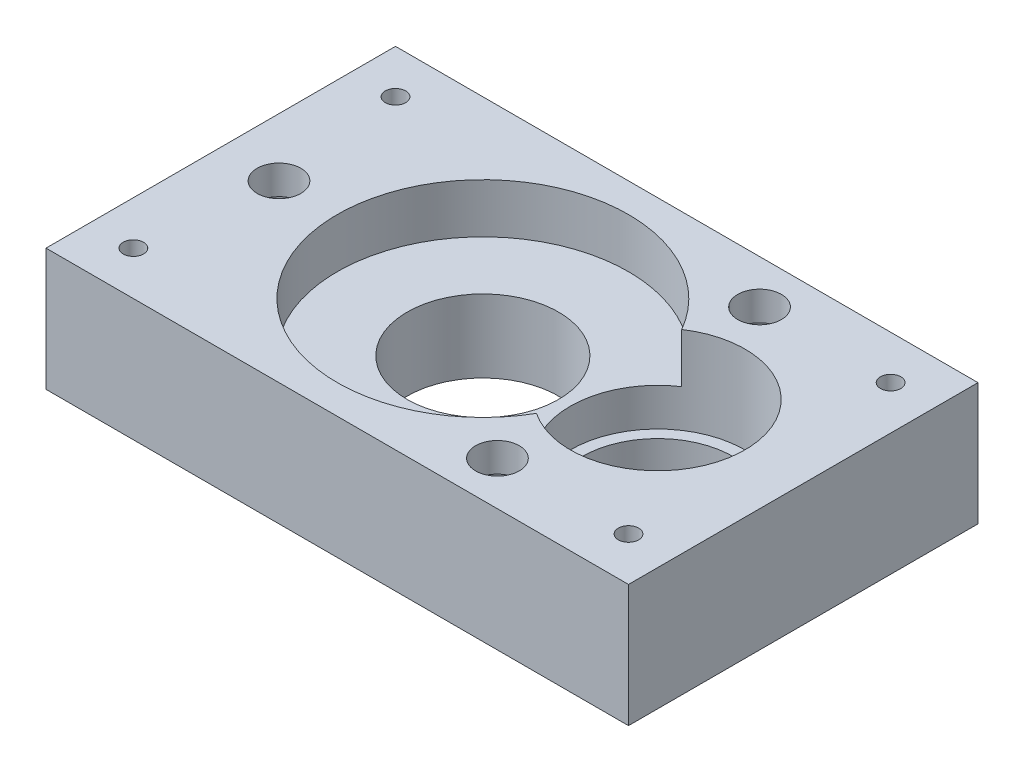
SolidWorks part; units mm, degrees
note: The reader was unsure of these and kept them because the rebuilt part matched: shared geometry of "草图1<13>", "草图1<14>", "草图3<4>".
ref_plane "前视基准面" through (0, 0, 0) normal (0, 0, 1) x (1, 0, 0)
ref_plane "上视基准面" through (0, 0, 0) normal (0, 1, 0) x (1, 0, 0)
ref_plane "右视基准面" through (0, 0, 0) normal (1, 0, 0) x (0, 0, -1)
other "Configuration Table"
sketch "草图1" plane through (0, 0, 0) normal (0, 1, 0) x (1, 0, 0)
  line L1 (0, 0) -> (20, 0)
  line L2 (0, 0) -> (0, -12)
  line L3 (0, -12) -> (20, -12)
  line L4 (20, 0) -> (20, -12)
  circle A4 centre (15, -6) radius 2.6
  circle A6 centre (7.8259, -8.9706) radius 0.6
  circle A8 centre (9.8163, -3.6294) radius 2.6
  circle A9 centre (9, -6) radius 2.6
  circle A10 centre (9, -6) radius 5
  circle A11 centre (15, -6) radius 3
  circle A12 centre (15, -6) radius 2.6
  dimension "D2" = 5.2
  dimension "D3" = 5.7
  dimension "D6" = 10
  dimension "D4" = 20
  dimension "D5" = 5.2
  dimension "D7" = 6
  dimension "D14" = 1.2
  dimension "D15" = 5.2
  dimension "D8" = 6
  dimension "D9" = 5.2
  dimension "D11" = 12
  dimension "D12" = 5.7
extrude "凸台-拉伸1" add sketch "草图1" along normal blind 3
extrude "凸台-拉伸3" add sketch "草图1<13>" along normal blind 1.3 and the other way blind 1.2 from surface at 0 contours L3 L4 L1 L2 | A11 | A9 starting at face at (10, 0, 6)
sketch "草图1<13>" plane through (0, 0, 0) normal (0, 1, 0) x (1, 0, 0) same geometry as "草图1"
extrude "凸台-拉伸4" add sketch "草图1<14>" along normal blind 1.2 from surface at -1.2 contours L4 L3 L2 L1 | A9 | A4 starting at face at (9, -1.2, 8.6)
sketch "草图1<14>" plane through (0, 0, 0) normal (0, 1, 0) x (1, 0, 0) same geometry as "草图1"
sketch "草图3" plane through (0, 0, 0) normal (0, 1, 0) x (1, 0, 0)
  circle A8 centre (2, -6) radius 0.75
  circle A9 centre (14, -1.5) radius 0.75
  circle A10 centre (14, -10.5) radius 0.75
  circle A11 centre (2, -6) radius 1
  circle A12 centre (14, -1.5) radius 1
  circle A13 centre (14, -10.5) radius 1
  circle A14 centre (1.5, -1.5) radius 0.35
  circle A15 centre (18.5, -1.5) radius 0.35
  circle A16 centre (1.5, -10.5) radius 0.35
  circle A17 centre (18.5, -10.5) radius 0.35
  dimension "D1" = 2
  dimension "D2" = 0.7
  dimension "D3" = 1.5
  dimension "D4" = 1.5
  dimension "D5" = 10.5
  dimension "D6" = 1.5
  dimension "D7" = 18.5
extrude "切除-拉伸3" cut sketch "草图3" along normal through all both and the other way through all
extrude "切除-拉伸4" cut sketch "草图3<4>" along normal offset from surface (3.2 mm away) 1 from surface at -1.2 contours A12 | A13 | A11 up to face at (18.5, 3, 1.85) starting at face at (18.5, -1.2, 1.85)
sketch "草图3<4>" plane through (0, 0, 0) normal (0, 1, 0) x (1, 0, 0) same geometry as "草图3"
